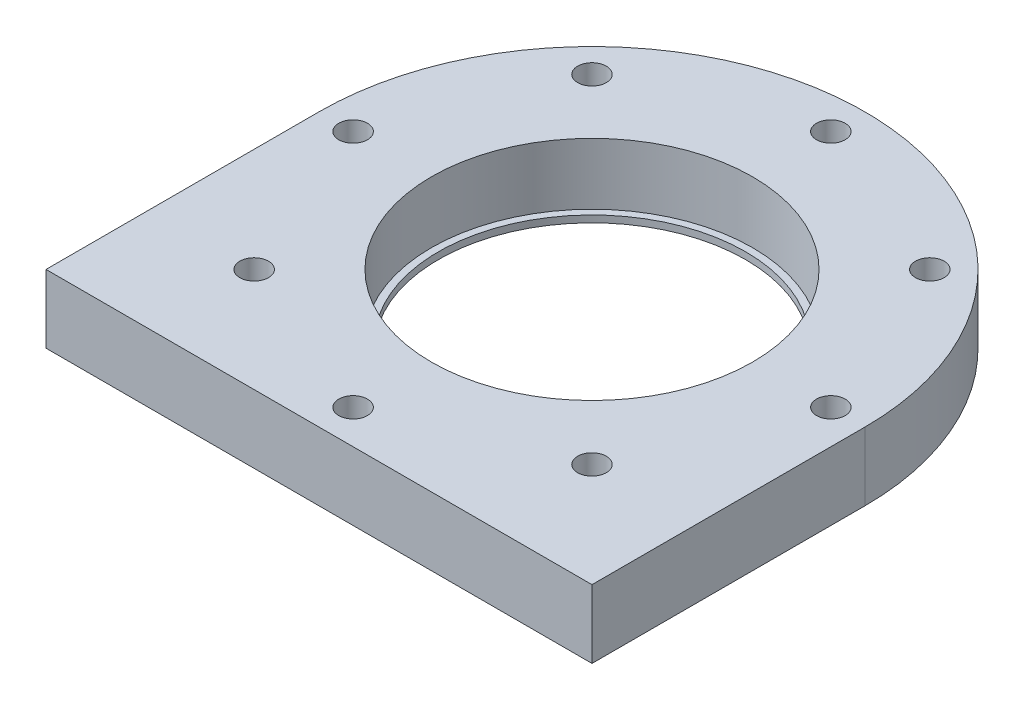
SolidWorks part; units mm, degrees
ref_plane "前视基准面" through (0, 0, 0) normal (0, 0, 1) x (1, 0, 0)
ref_plane "上视基准面" through (0, 0, 0) normal (0, 1, 0) x (1, 0, 0)
ref_plane "右视基准面" through (0, 0, 0) normal (1, 0, 0) x (0, 0, -1)
other "Configuration Table"
sketch "草图1" plane through (0, 0, 0) normal (0, 1, 0) x (1, 0, 0)
  line L2 (-40, 0) -> (-40, -40)
  line L3 (-40, -40) -> (40, -40)
  line L4 (40, 0) -> (40, -40)
  arc A0 (40, 0) -> (-40, 0) centre (0, 0) ccw
  circle A1 centre (0, 0) radius 22.5
  dimension "D1" = 80
  dimension "D2" = 45
extrude "凸台-拉伸1" add sketch "草图1" along normal blind 10
sketch "草图2" plane through (0, 10, 0) normal (0, 1, 0) x (1, 0, 0)
  circle A0 centre (0, 0) radius 35 construction
  circle A1 centre (0, 35) radius 2.1
  circle A2 centre (24.7487, 24.7487) radius 2.1
  circle A3 centre (35, 0) radius 2.1
  circle A4 centre (24.7487, -24.7487) radius 2.1
  circle A5 centre (0, -35) radius 2.1
  circle A6 centre (-24.7487, -24.7487) radius 2.1
  circle A7 centre (-35, 0) radius 2.1
  circle A8 centre (-24.7487, 24.7487) radius 2.1
  point P21 (0, 0)
  dimension "D1" = 70
  dimension "D2" = 4.2
  dimension "D3" = 8
extrude "切除-拉伸1" cut sketch "草图2" against normal through all
sketch "草图5" plane through (0, 10, 0) normal (0, 1, 0) x (1, 0, 0)
  circle A0 centre (0, 0) radius 23.525
  dimension "D1" = 47.05
extrude "切除-拉伸2" cut sketch "草图5" against normal blind 9
